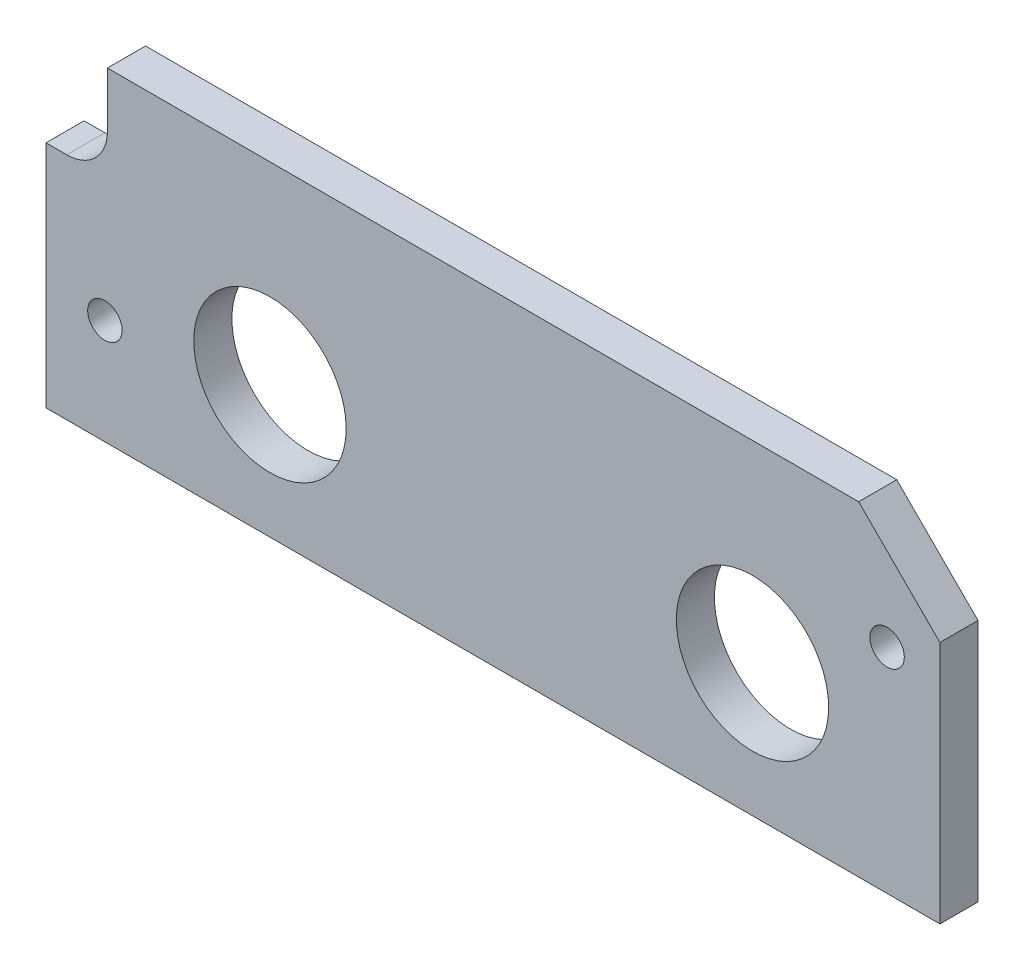
SolidWorks part; units mm, degrees
material "Acrylic (Medium-high impact)"
ref_plane "Front Plane" through (0, 0, 0) normal (0, 0, 1) x (1, 0, 0)
ref_plane "Top Plane" through (0, 0, 0) normal (0, 1, 0) x (1, 0, 0)
ref_plane "Right Plane" through (0, 0, 0) normal (1, 0, 0) x (0, 0, -1)
sketch "Sketch1" plane through (0, 0, 0) normal (0, 0, 1) x (1, 0, 0)
  line L7 (-133.0325, 57.658) -> (-133.0325, 50.8)
  line L8 (-138.1125, 45.72) -> (-140.716, 45.72)
  line L9 (-140.716, 45.72) -> (-140.716, 17.018)
  line L10 (-140.716, 17.018) -> (-28.956, 17.018)
  line L11 (-28.956, 17.018) -> (-28.956, 47.498)
  line L12 (-28.956, 47.498) -> (-39.116, 57.658)
  line L13 (-39.116, 57.658) -> (-133.0325, 57.658)
  line L14 (-133.0325, 57.658) -> (-133.0325, 50.8)
  line L15 (-138.1125, 45.72) -> (-140.716, 45.72)
  line L16 (-140.716, 45.72) -> (-140.716, 17.018)
  line L17 (-140.716, 17.018) -> (-28.956, 17.018)
  line L18 (-28.956, 17.018) -> (-28.956, 47.498)
  line L19 (-28.956, 47.498) -> (-39.116, 57.658)
  line L20 (-39.116, 57.658) -> (-133.0325, 57.658)
  arc A1 (-138.1125, 45.72) -> (-133.0325, 50.8) centre (-138.1125, 50.8) ccw
  arc A2 (-138.1125, 45.72) -> (-133.0325, 50.8) centre (-138.1125, 50.8) ccw
  dimension "D1" = 0
extrude "Boss-Extrude1" add sketch "Sketch1" along normal blind 4.7625
hole_wizard "#6 Clearance Hole1" positions "Sketch3" profile "Sketch2" hole size "#6" standard "ANSI Inch" end condition through all
sketch "Sketch3" plane through (0, 0, 4.7625) normal (0, 0, 1) x (1, 0, 0)
  point P0 (-133.35, 30.1625)
  point P3 (-35.56, 43.688)
sketch "Sketch2" plane through (-133.35, 30.1625, 4.7625) normal (1, 0, 0) x (0, -1, 0)
  line L0 (0, 0) -> (0, 4.7625)
  line L1 (0, 4.7625) -> (2.1526, 4.7625)
  line L2 (2.1526, 4.7625) -> (2.1526, 0)
  line L5 (2.1526, 0) -> (0, 0)
  line L11 (0, -6.35) -> (0, 107.95) construction
  dimension "Thru Hole Dia." = 4.3053
  dimension "Thru Hole Depth" = 4.7625
hole_wizard "3/4 (0.75) Diameter Hole1" positions "Sketch5" profile "Sketch4" hole size "3/4" standard "ANSI Inch" end condition through all
sketch "Sketch5" plane through (0, 0, 4.7625) normal (0, 0, 1) x (1, 0, 0)
  point P0 (-112.7125, 33.528)
  point P3 (-52.3875, 33.528)
sketch "Sketch4" plane through (-112.7125, 33.528, 4.7625) normal (1, 0, 0) x (0, -1, 0)
  line L0 (0, 0) -> (0, 4.7625)
  line L1 (0, 4.7625) -> (9.525, 4.7625)
  line L2 (9.525, 4.7625) -> (9.525, 0)
  line L5 (9.525, 0) -> (0, 0)
  line L11 (0, -6.35) -> (0, 107.95) construction
  dimension "Thru Hole Dia." = 19.05
  dimension "Thru Hole Depth" = 4.7625
